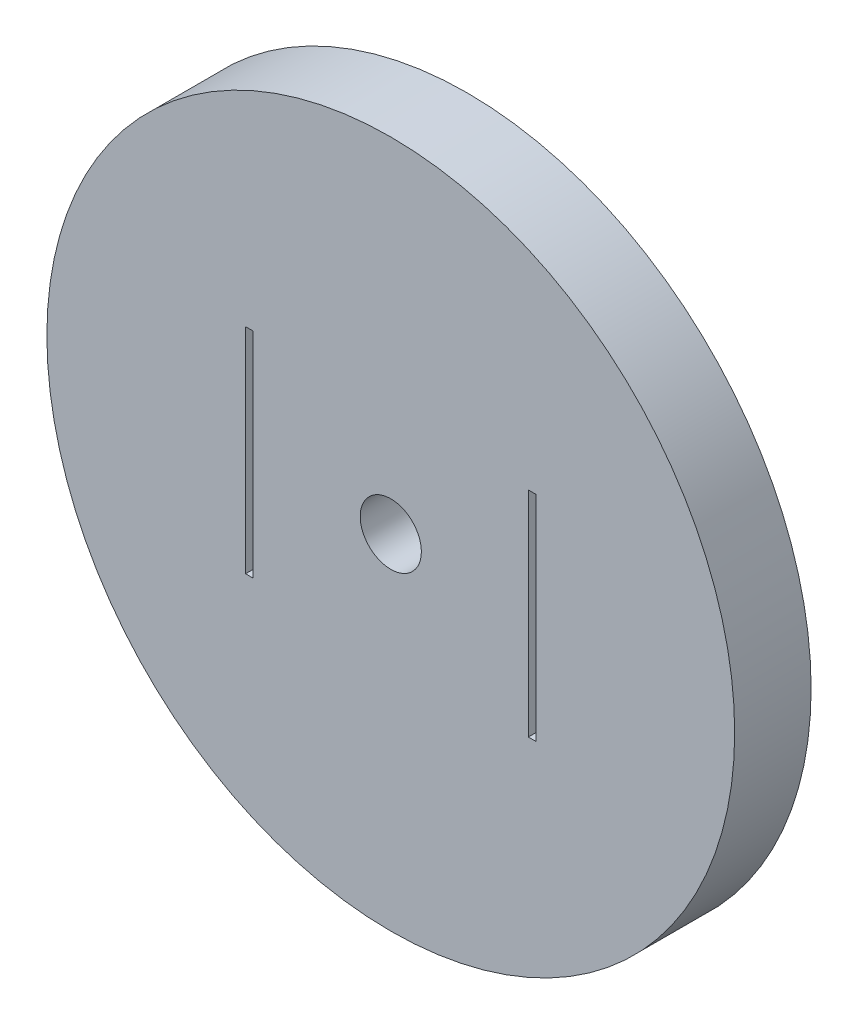
SolidWorks part; units mm, degrees
ref_plane "Front Plane" through (0, 0, 0) normal (0, 0, 1) x (1, 0, 0)
ref_plane "Top Plane" through (0, 0, 0) normal (0, 1, 0) x (1, 0, 0)
ref_plane "Right Plane" through (0, 0, 0) normal (1, 0, 0) x (0, 0, -1)
sketch "Sketch1" plane through (0, 0, 0) normal (0, 0, 1) x (1, 0, 0)
  line L0 (0, 10.3237) -> (0, -11.9962) construction
  line L1 (-9.5, 7) -> (-9, 7)
  line L2 (-9.5, 7) -> (-9.5, -7)
  line L3 (-9.5, -7) -> (-9, -7)
  line L4 (-9, 7) -> (-9, -7)
  line L5 (9, 7) -> (9, -7)
  line L6 (9.5, -7) -> (9, -7)
  line L7 (9.5, 7) -> (9.5, -7)
  line L8 (9.5, 7) -> (9, 7)
  circle A0 centre (0, 0) radius 22.5
  circle A1 centre (0, 0) radius 2
  dimension "D1" = 4
  dimension "D2" = 45
  dimension "D3" = 0.5
  dimension "D4" = 9
  dimension "D5" = 7
  dimension "D6" = 7
extrude "Boss-Extrude1" add sketch "Sketch1" along normal blind 5
sketch "Sketch3" plane through (0, 0, 0) normal (0, 1, 0) x (1, 0, 0)
  line L0 (-14.5, 9.5) -> (-14.5, 0) construction
  line L1 (22.5, 0) -> (-22.5, 0) construction
  line L2 (-17, 9.5) -> (-17, 0)
  line L3 (-17, 0) -> (-14.5, 0)
  line L4 (-14.5, 0) -> (-14.5, 12)
  line L5 (-22.5, 0) -> (-22.5, -5) construction
  circle A0 centre (-14.5, 9.5) radius 2.5 construction
  arc A1 (-17, 9.5) -> (-14.5, 12) centre (-14.5, 9.5) cw
  dimension "D1" = 5
  dimension "D2" = 8
  dimension "D3" = 12
revolve "Revolve1" add sketch "Sketch3" angle 360 about L0
